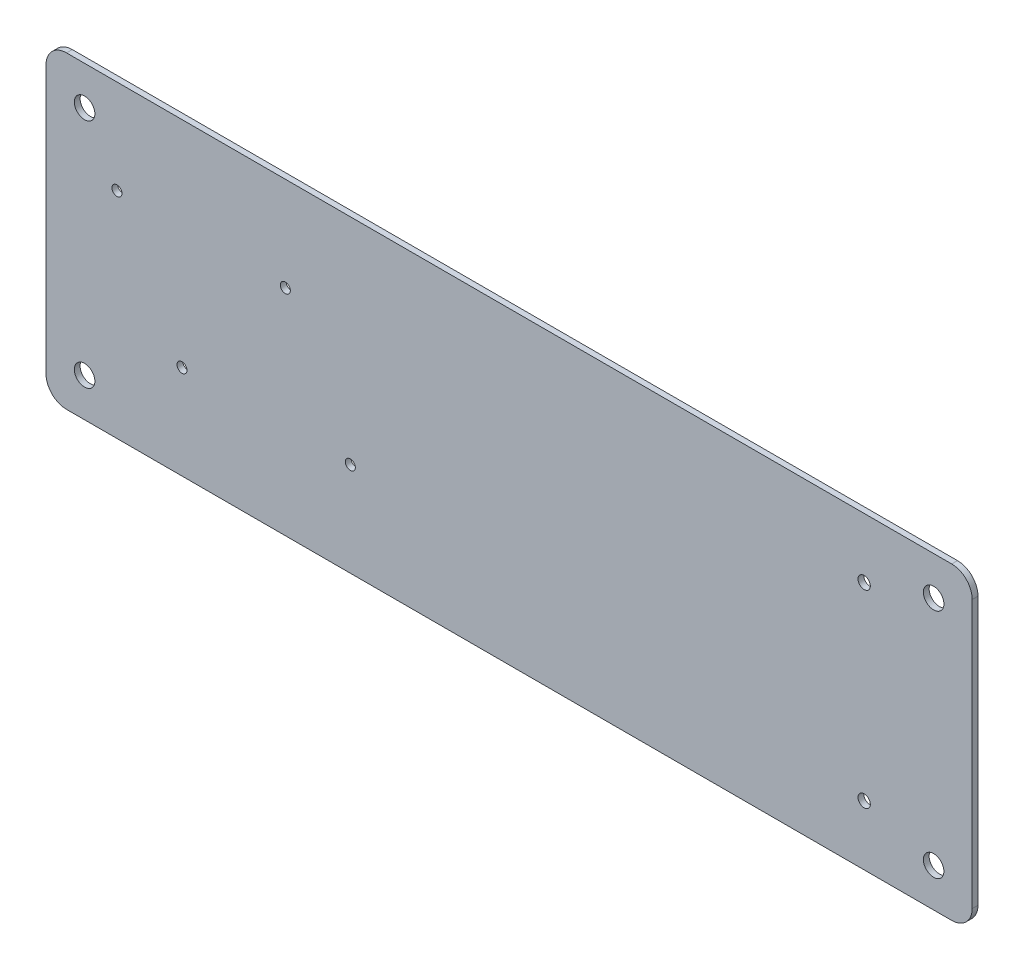
SolidWorks part; units mm, degrees
ref_plane "Front Plane" through (0, 0, 0) normal (0, 0, 1) x (1, 0, 0)
ref_plane "Top Plane" through (0, 0, 0) normal (0, 1, 0) x (1, 0, 0)
ref_plane "Right Plane" through (0, 0, 0) normal (1, 0, 0) x (0, 0, -1)
sketch "Sketch1" plane through (0, 0, 0) normal (0, 0, 1) x (1, 0, 0)
  line L1 (-145.6436, -50.8) -> (145.6436, -50.8)
  line L2 (-152.4, -44.0436) -> (-152.4, 44.0436)
  line L3 (-145.6436, 50.8) -> (145.6436, 50.8)
  line L4 (152.4, -44.0436) -> (152.4, 44.0436)
  line L5 (-152.4, -50.8) -> (152.4, 50.8) construction
  line L6 (-152.4, 50.8) -> (152.4, -50.8) construction
  arc A0 (145.6436, -50.8) -> (152.4, -44.0436) centre (145.6436, -44.0436) ccw
  arc A1 (-152.4, 44.0436) -> (-145.6436, 50.8) centre (-145.6436, 44.0436) cw
  arc A2 (-145.6436, -50.8) -> (-152.4, -44.0436) centre (-145.6436, -44.0436) cw
  arc A3 (145.6436, 50.8) -> (152.4, 44.0436) centre (145.6436, 44.0436) cw
  point P0 (0, 0)
  dimension "D3" = 6.7564
  dimension "D1" = 101.6
  dimension "D2" = 304.8
extrude "Boss-Extrude1" add sketch "Sketch1" along normal blind 1.9
sketch "Sketch2" plane through (0, 0, 0) normal (0, 0, -1) x (-1, 0, 0)
  line L0 (-139.7, 38.1) -> (-139.7, -38.1) construction
  line L1 (-139.7, 38.1) -> (139.7, 38.1) construction
  line L5 (55, 0) -> (-55, 0) construction
  line L6 (0, 55) -> (0, -55) construction
  circle A0 centre (-139.7, 38.1) radius 3.3782
  circle A1 centre (-139.7, -38.1) radius 3.3782
  circle A2 centre (139.7, 38.1) radius 3.3782
  circle A3 centre (139.7, -38.1) radius 3.3782
  point P4 (0, 0)
  dimension "D1" = 6.7564
  dimension "D2" = 76.2
  dimension "D3" = 279.4
extrude "Cut-Extrude1" cut sketch "Sketch2" against normal up to next and the other way through all
sketch "Sketch3" plane through (0, 0, 1.9) normal (0, 0, 1) x (1, 0, 0)
  circle A0 centre (-107.65, -19.85) radius 1.65
  arc A1 (-107.65, -21.5) -> (-107.65, -18.2) centre (-107.65, -19.85) ccw construction
  circle A2 centre (-129.05, 19.85) radius 1.65
  arc A3 (-129.05, 21.5) -> (-129.05, 18.2) centre (-129.05, 19.85) ccw construction
  circle A4 centre (-52.25, -19.85) radius 1.65
  arc A5 (-52.25, -18.2) -> (-52.25, -21.5) centre (-52.25, -19.85) ccw construction
  circle A6 centre (-73.65, 19.85) radius 1.65
  arc A7 (-73.65, 21.5) -> (-73.65, 18.2) centre (-73.65, 19.85) ccw construction
  circle A8 centre (116.84, -31.115) radius 2.0193
  circle A9 centre (116.84, 31.115) radius 2.0193
  ellipse E0 centre (116.84, 31.115) end of major axis (118.8593, 31.115) minor radius 2.0193 construction
  ellipse E1 centre (116.84, -31.115) end of major axis (118.8593, -31.115) minor radius 2.0193 construction
extrude "Cut-Extrude2" cut sketch "Sketch3" against normal up to next
